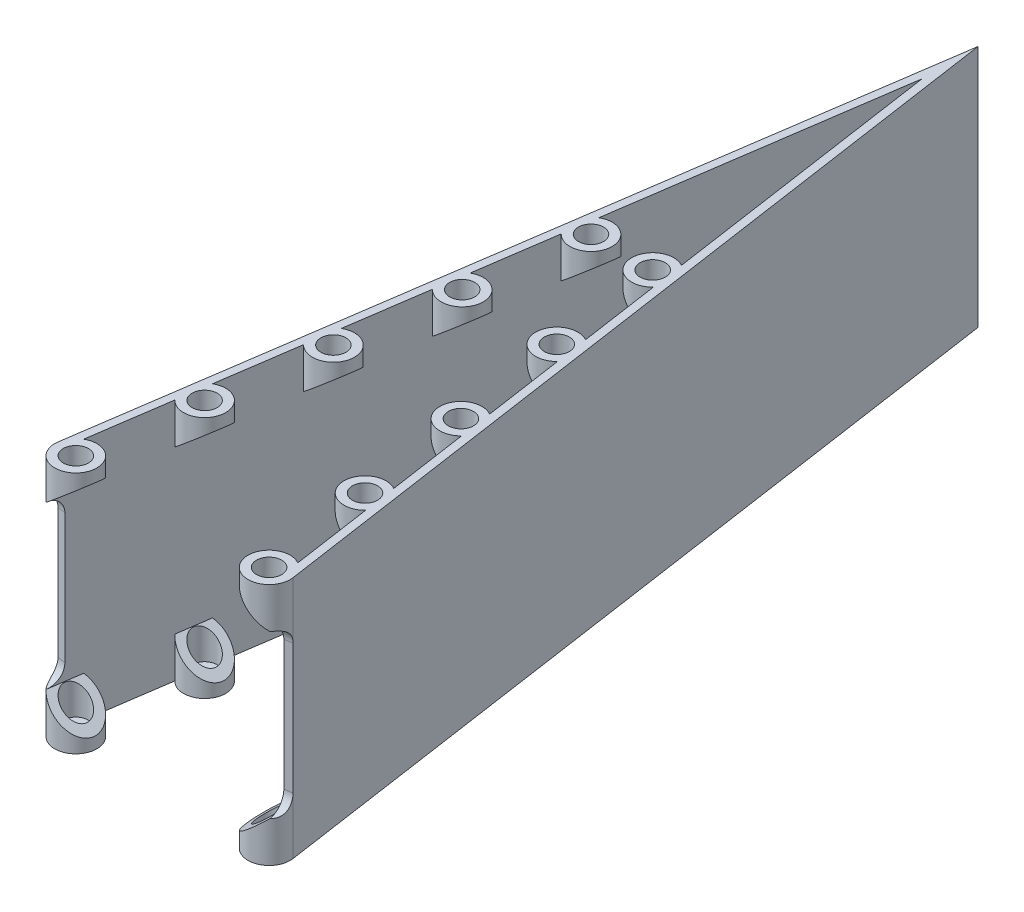
SolidWorks part; units mm, degrees
ref_plane "Front Plane" through (0, 0, 0) normal (0, 0, 1) x (1, 0, 0)
ref_plane "Top Plane" through (0, 0, 0) normal (0, 1, 0) x (1, 0, 0)
ref_plane "Right Plane" through (0, 0, 0) normal (1, 0, 0) x (0, 0, -1)
sketch "Sketch1" plane through (0, 0, 0) normal (0, 1, 0) x (1, 0, 0)
  line L0 (-13.5, 0) -> (13.5, 0) construction
  line L1 (-13.5, 0) -> (0, 92.188)
  line L2 (0, 92.188) -> (13.5, 0)
  line L3 (13.5, 0) -> (14.4894, 0.1449)
  line L4 (14.4894, 0.1449) -> (0, 99.0896)
  line L5 (0, 99.0896) -> (-14.4894, 0.1449)
  line L6 (-14.4894, 0.1449) -> (-13.5, 0)
  point P2 (0, 0)
  dimension "D1" = 90
  dimension "D2" = 90
  dimension "D4" = 1
  dimension "D3" = 100
  dimension "D5" = 27
extrude "Boss-Extrude1" add sketch "Sketch1" along normal blind 30
sketch "Sketch2" plane through (0, 0, 0) normal (0, 1, 0) x (1, 0, 0)
  line L0 (0, -1000) -> (0, 49000) construction
  line L1 (0, 92.188) -> (13.5, 0) construction
  line L2 (0, 92.188) -> (13.5, 0) construction
  line L3 (11.9169, -0.2318) -> (13.5, 0) construction
  line L4 (13.5, 0) -> (14.4894, 0.1449) construction
  line L5 (14.4894, 0.1449) -> (0, 99.0896) construction
  line L6 (14.4894, 0.1449) -> (0, 99.0896) construction
  circle A0 centre (11.9169, -0.2318) radius 2.6
  circle A1 centre (11.9169, -0.2318) radius 1.55
  circle A2 centre (9.8884, 13.6204) radius 1.55
  circle A3 centre (9.8884, 13.6204) radius 2.6
  circle A4 centre (7.8598, 27.4727) radius 1.55
  circle A5 centre (7.8598, 27.4727) radius 2.6
  circle A6 centre (5.8313, 41.3249) radius 1.55
  circle A7 centre (5.8313, 41.3249) radius 2.6
  circle A8 centre (3.8028, 55.1772) radius 1.55
  circle A9 centre (3.8028, 55.1772) radius 2.6
  circle A12 centre (-11.9169, -0.2318) radius 2.6
  circle A13 centre (-11.9169, -0.2318) radius 1.55
  circle A14 centre (-9.8884, 13.6204) radius 2.6
  circle A15 centre (-9.8884, 13.6204) radius 1.55
  circle A16 centre (-7.8598, 27.4727) radius 2.6
  circle A17 centre (-7.8598, 27.4727) radius 1.55
  circle A18 centre (-5.8313, 41.3249) radius 2.6
  circle A19 centre (-5.8313, 41.3249) radius 1.55
  circle A20 centre (-3.8028, 55.1772) radius 2.6
  circle A21 centre (-3.8028, 55.1772) radius 1.55
  dimension "D1" = 5.2
  dimension "D2" = 3.1
  dimension "D4" = 14
  dimension "D3" = 5
extrude "Boss-Extrude3" add sketch "Sketch2" along normal blind 5
sketch "Sketch4" plane through (0.2834, 0, 1.9354) normal (0.1449, 0, 0.9894) x (0.9894, 0, -0.1449)
  line L0 (9.1575, 5) -> (9.1575, 0) construction
  line L1 (14.3575, 5) -> (9.1575, 5) construction
  line L2 (13.3575, 30) -> (13.3575, 0) construction
  line L3 (9.1575, 5) -> (9.1575, 0) construction
  line L4 (14.3575, 5) -> (9.1575, 5) construction
  line L5 (13.3575, 30) -> (13.3575, 0) construction
  line L6 (13.3575, 5) -> (9.1575, 1.4758)
  line L7 (13.3575, 5) -> (9.1575, 5)
  line L8 (9.1575, 5) -> (9.1575, 1.4758)
  dimension "D1" = 40
extrude "Cut-Extrude1" cut sketch "Sketch4" against normal up to surface and the other way through all contours L7 L8 L6 region at (10.7295, 3.8253, 0.4057) up to face at (-8.5575, 5, -33.751)
sketch "Sketch5" plane through (-0.2834, 0, 1.9354) normal (-0.1449, 0, 0.9894) x (0.9894, 0, 0.1449)
  line L0 (-9.1575, 0) -> (-9.1575, 5) construction
  line L1 (-9.1575, 5) -> (-14.3575, 5) construction
  line L2 (-13.3575, 30) -> (-13.3575, 0) construction
  line L3 (-9.1575, 0) -> (-9.1575, 5) construction
  line L4 (-9.1575, 5) -> (-14.3575, 5) construction
  line L5 (-13.3575, 30) -> (-13.3575, 0) construction
  line L6 (-13.3575, 5) -> (-9.1575, 1.4758)
  line L7 (-13.3575, 5) -> (-9.1575, 5)
  line L8 (-9.1575, 5) -> (-9.1575, 1.4758)
  dimension "D1" = 40
extrude "Cut-Extrude2" cut sketch "Sketch5" against normal up to surface and the other way through all contours L8 L7 L6 region at (-10.7295, 3.8253, 0.4057) up to face at (8.5575, 5, -33.751)
ref_plane "Plane1" through (0, 15, 0) normal (0, 1, 0) x (1, 0, 0)
mirror "Mirror2" about plane through (0, 15, 0) normal (0, 1, 0) of "Cut-Extrude2", "Cut-Extrude1", "Boss-Extrude3"
fillet "Fillet1" radius 2 4 edges at (-13.9947, 5, -0.0724) (13.9947, 5, -0.0724) (13.9947, 25, -0.0724) (-13.9947, 25, -0.0724)
sketch "Sketch6" plane through (0, 0, 0) normal (0, -1, 0) x (1, 0, 0)
  arc A0 (-13.2031, -2.0278) -> (-14.4894, -0.1449) centre (-11.9169, 0.2318) ccw construction
  arc A1 (14.4894, -0.1449) -> (13.2031, -2.0278) centre (11.9169, 0.2318) ccw construction
  arc A2 (11.7684, -11.8245) -> (11.1745, -15.88) centre (9.8884, -13.6204) ccw construction
  arc A3 (-11.1745, -15.88) -> (-11.7684, -11.8245) centre (-9.8884, -13.6204) ccw construction
  arc A4 (-9.146, -29.7323) -> (-9.7399, -25.6768) centre (-7.8598, -27.4727) ccw construction
  arc A5 (9.7399, -25.6768) -> (9.146, -29.7323) centre (7.8598, -27.4727) ccw construction
  arc A6 (7.7114, -39.529) -> (7.1175, -43.5845) centre (5.8313, -41.3249) ccw construction
  arc A7 (-7.1175, -43.5845) -> (-7.7114, -39.529) centre (-5.8313, -41.3249) ccw construction
  arc A8 (-5.089, -57.4368) -> (-5.6829, -53.3813) centre (-3.8028, -55.1772) ccw construction
  arc A9 (5.6829, -53.3813) -> (5.089, -57.4368) centre (3.8028, -55.1772) ccw construction
  arc A10 (-13.2031, -2.0278) -> (-14.4894, -0.1449) centre (-11.9169, 0.2318) ccw
  arc A11 (14.4894, -0.1449) -> (13.2031, -2.0278) centre (11.9169, 0.2318) ccw
  arc A12 (11.7684, -11.8245) -> (11.1745, -15.88) centre (9.8884, -13.6204) ccw
  arc A13 (-11.1745, -15.88) -> (-11.7684, -11.8245) centre (-9.8884, -13.6204) ccw
  arc A14 (-9.146, -29.7323) -> (-9.7399, -25.6768) centre (-7.8598, -27.4727) ccw
  arc A15 (9.7399, -25.6768) -> (9.146, -29.7323) centre (7.8598, -27.4727) ccw
  arc A16 (7.7114, -39.529) -> (7.1175, -43.5845) centre (5.8313, -41.3249) ccw
  arc A17 (-7.1175, -43.5845) -> (-7.7114, -39.529) centre (-5.8313, -41.3249) ccw
  arc A18 (-5.089, -57.4368) -> (-5.6829, -53.3813) centre (-3.8028, -55.1772) ccw
  arc A19 (5.6829, -53.3813) -> (5.089, -57.4368) centre (3.8028, -55.1772) ccw
  circle A20 centre (3.8028, -55.1772) radius 2.6
  circle A21 centre (-3.8028, -55.1772) radius 2.6
  circle A22 centre (5.8313, -41.3249) radius 2.6
  circle A23 centre (-5.8313, -41.3249) radius 2.6
  circle A24 centre (7.8598, -27.4727) radius 2.6
  circle A25 centre (-7.8598, -27.4727) radius 2.6
  circle A26 centre (-9.8884, -13.6204) radius 2.6
  circle A27 centre (9.8884, -13.6204) radius 2.6
  circle A28 centre (11.9169, 0.2318) radius 2.6
  circle A29 centre (-11.9169, 0.2318) radius 2.6
  circle M23 centre (11.9169, 0.2318) radius 1.55
  circle M24 centre (9.8884, -13.6204) radius 1.55
  circle M25 centre (7.8598, -27.4727) radius 1.55
  circle M26 centre (5.8313, -41.3249) radius 1.55
  circle M27 centre (3.8028, -55.1772) radius 1.55
  circle M28 centre (-5.8313, -41.3249) radius 1.55
  circle M29 centre (-9.8884, -13.6204) radius 1.55
  circle M30 centre (-11.9169, 0.2318) radius 1.55
  circle M31 centre (-7.8598, -27.4727) radius 1.55
  circle M32 centre (-3.8028, -55.1772) radius 1.55
extrude "Boss-Extrude4" add sketch "Sketch6" against normal blind 1 contours M27 | M32 | M28 | M26 | M25 | M31 | M29 | M24 | M23 | M30 region at (11.9169, 0, 0.2318) region at (9.8884, 0, -13.6204) region at (7.8598, 0, -27.4727) region at (5.8313, 0, -41.3249) region at (3.8028, 0, -55.1772) region at (-5.8313, 0, -41.3249) region at (-9.8884, 0, -13.6204) region at (-11.9169, 0, 0.2318) region at (-7.8598, 0, -27.4727) region at (-3.8028, 0, -55.1772)
equation "\"D2@Sketch1\"=\"D1@Sketch1\""
